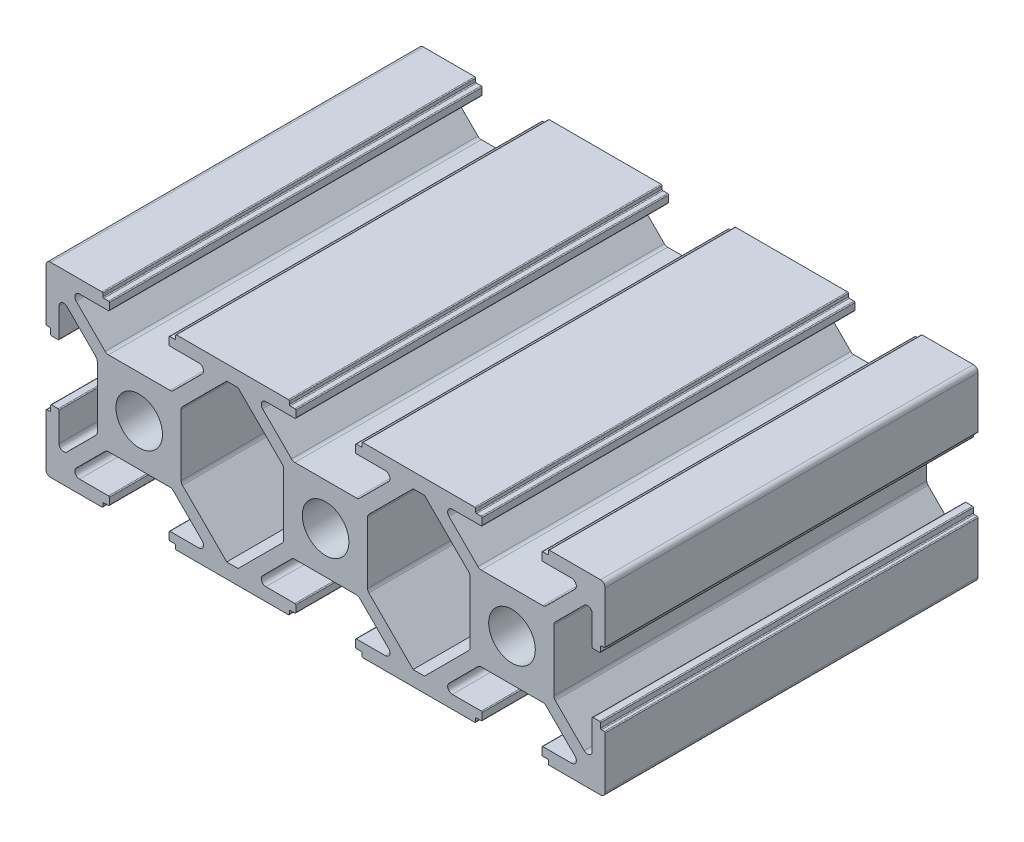
SolidWorks part; units mm, degrees
material "6061 Alaşım"
ref_plane "Ön Düzlem" through (0, 0, 0) normal (0, 0, 1) x (1, 0, 0)
ref_plane "Üst Düzlem" through (0, 0, 0) normal (0, 1, 0) x (1, 0, 0)
ref_plane "Sağ Düzlem" through (0, 0, 0) normal (1, 0, 0) x (0, 0, -1)
sketch "Çizim1" plane through (0, 0, 0) normal (0, 0, 1) x (1, 0, 0)
  line L0 (0, 0) -> (10, 10)
  line L1 (10, -10) -> (-10, -10)
  line L2 (10, -10) -> (10, 10)
  line L3 (10, 10) -> (-10, 10)
  line L4 (-10, -10) -> (-10, 10)
  line L5 (0, 10) -> (0, -10)
  line L6 (10, 0) -> (-10, 0)
  line L7 (4.5, 3.5101) -> (10, 9.0101)
  line L8 (3.5101, 4.5) -> (9.0101, 10)
  line L9 (10, 3.2) -> (8.6, 3.2)
  line L10 (8.6, 3.3) -> (8.6, 6.4029)
  line L11 (6.4029, 8.6) -> (3.3, 8.6)
  line L12 (3.2, 8.6) -> (3.2, 10)
  line L13 (3.6565, 4.6464) -> (6.7565, 7.7464)
  line L14 (7.7464, 6.7565) -> (4.6464, 3.6565)
  line L15 (3.2, 10) -> (9.5, 10)
  line L16 (10, 9.5) -> (10, 3.2)
  line L17 (4.5, 3.3029) -> (4.5, 0)
  line L18 (3.3029, 4.5) -> (0, 4.5)
  line L19 (3.3, 9.5) -> (3.8, 9.5)
  line L20 (3.9, 9.6) -> (3.9, 9.9)
  line L21 (3.2, 9.4) -> (3.2, 8.7)
  line L22 (4, 10) -> (9.5, 10)
  line L23 (9.5, 3.3) -> (9.5, 3.8)
  line L24 (9.6, 3.9) -> (9.9, 3.9)
  line L25 (8.7, 3.2) -> (9.4, 3.2)
  line L26 (10, 4) -> (10, 9.5)
  line L27 (0, 0) -> (10, -10)
  line L28 (3.3029, -4.5) -> (0, -4.5)
  line L29 (6.7565, -7.7464) -> (3.6565, -4.6464)
  line L30 (3.3, -8.6) -> (6.4029, -8.6)
  line L31 (3.2, -8.7) -> (3.2, -9.4)
  line L32 (3.3, -9.5) -> (3.8, -9.5)
  line L33 (3.9, -9.6) -> (3.9, -9.9)
  line L34 (4, -10) -> (9.5, -10)
  line L35 (10, -4) -> (10, -9.5)
  line L36 (9.6, -3.9) -> (9.9, -3.9)
  line L37 (9.5, -3.3) -> (9.5, -3.8)
  line L38 (9.4, -3.2) -> (8.7, -3.2)
  line L39 (8.6, -6.4029) -> (8.6, -3.3)
  line L40 (4.6464, -3.6565) -> (7.7464, -6.7565)
  line L41 (4.5, -3.3029) -> (4.5, 0)
  line L42 (0, 0) -> (-10, -10)
  line L43 (-4.5, -3.3029) -> (-4.5, 0)
  line L44 (-7.7464, -6.7565) -> (-4.6464, -3.6565) construction
  line L45 (-4.6464, 3.6565) -> (-9.3899, 8.4)
  line L46 (-9.3899, 8.4) -> (-10, 8.4)
  line L47 (-10, -8.4) -> (-9.3899, -8.4)
  line L48 (-9.3899, -8.4) -> (-4.6464, -3.6565)
  line L49 (-10, -4) -> (-10, -9.5)
  line L50 (-4, -10) -> (-9.5, -10)
  line L51 (-3.9, -9.6) -> (-3.9, -9.9)
  line L52 (-3.3, -9.5) -> (-3.8, -9.5)
  line L53 (-3.2, -9.4) -> (-3.2, -8.7)
  line L54 (-6.4029, -8.6) -> (-3.3, -8.6)
  line L55 (-3.6565, -4.6464) -> (-6.7565, -7.7464)
  line L56 (-3.3029, -4.5) -> (0, -4.5)
  line L57 (0, 0) -> (-10, 10)
  line L58 (-3.3029, 4.5) -> (0, 4.5)
  line L59 (-6.7565, 7.7464) -> (-3.6565, 4.6464)
  line L60 (-3.3, 8.6) -> (-6.4029, 8.6)
  line L61 (-3.2, 8.7) -> (-3.2, 9.4)
  line L62 (-3.3, 9.5) -> (-3.8, 9.5)
  line L63 (-3.9, 9.6) -> (-3.9, 9.9)
  line L64 (-4, 10) -> (-9.5, 10)
  line L65 (-10, 4) -> (-10, 9.5)
  line L70 (-4.6464, 3.6565) -> (-7.7464, 6.7565) construction
  line L71 (-4.5, 3.3029) -> (-4.5, 0)
  line L72 (-9.4, 3.2) -> (-8.7, 3.2) [skipped]
  line L73 (-8.6, 6.4029) -> (-8.6, 3.3) [skipped]
  line L74 (-9.5, 3.3) -> (-9.5, 3.8) [skipped]
  line L75 (-9.6, 3.9) -> (-9.9, 3.9) [skipped]
  line L76 (-8.6, -3.3) -> (-8.6, -6.4029) [skipped]
  line L77 (-9.6, -3.9) -> (-9.9, -3.9) [skipped]
  line L78 (-9.5, -3.3) -> (-9.5, -3.8) [skipped]
  line L79 (-8.7, -3.2) -> (-9.4, -3.2) [skipped]
  circle A0 centre (0, 0) radius 2.5
  arc A1 (10, 9.5) -> (9.5, 10) centre (9.5, 9.5) ccw
  arc A2 (4.5, 3.3029) -> (4.6464, 3.6565) centre (5, 3.3029) cw
  arc A3 (3.6565, 4.6464) -> (3.3029, 4.5) centre (3.3029, 5) cw
  arc A4 (8.6, 6.4029) -> (7.7464, 6.7565) centre (8.1, 6.4029) ccw
  arc A5 (6.4029, 8.6) -> (6.7565, 7.7464) centre (6.4029, 8.1) cw
  arc A6 (9.5, 3.8) -> (9.6, 3.9) centre (9.6, 3.8) cw
  arc A7 (9.9, 3.9) -> (10, 4) centre (9.9, 4) ccw
  arc A8 (8.7, 3.2) -> (8.6, 3.3) centre (8.7, 3.3) cw
  arc A9 (9.5, 3.3) -> (9.4, 3.2) centre (9.4, 3.3) cw
  arc A10 (3.3, 8.6) -> (3.2, 8.7) centre (3.3, 8.7) cw
  arc A11 (3.8, 9.5) -> (3.9, 9.6) centre (3.8, 9.6) ccw
  arc A12 (3.9, 9.9) -> (4, 10) centre (4, 9.9) cw
  arc A13 (3.3, 9.5) -> (3.2, 9.4) centre (3.3, 9.4) ccw
  arc A14 (3.3029, -4.5) -> (3.6565, -4.6464) centre (3.3029, -5) cw
  arc A15 (6.4029, -8.6) -> (6.7565, -7.7464) centre (6.4029, -8.1) ccw
  arc A16 (3.2, -8.7) -> (3.3, -8.6) centre (3.3, -8.7) cw
  arc A17 (3.3, -9.5) -> (3.2, -9.4) centre (3.3, -9.4) cw
  arc A18 (3.8, -9.5) -> (3.9, -9.6) centre (3.8, -9.6) cw
  arc A19 (3.9, -9.9) -> (4, -10) centre (4, -9.9) ccw
  arc A20 (9.5, -10) -> (10, -9.5) centre (9.5, -9.5) ccw
  arc A21 (9.9, -3.9) -> (10, -4) centre (9.9, -4) cw
  arc A22 (9.5, -3.8) -> (9.6, -3.9) centre (9.6, -3.8) ccw
  arc A23 (9.5, -3.3) -> (9.4, -3.2) centre (9.4, -3.3) ccw
  arc A24 (8.6, -3.3) -> (8.7, -3.2) centre (8.7, -3.3) cw
  arc A25 (8.6, -6.4029) -> (7.7464, -6.7565) centre (8.1, -6.4029) cw
  arc A26 (4.6464, -3.6565) -> (4.5, -3.3029) centre (5, -3.3029) cw
  arc A27 (-4.5, -3.3029) -> (-4.6464, -3.6565) centre (-5, -3.3029) cw
  arc A34 (-3.9, -9.9) -> (-4, -10) centre (-4, -9.9) cw
  arc A35 (-3.8, -9.5) -> (-3.9, -9.6) centre (-3.8, -9.6) ccw
  arc A36 (-3.3, -9.5) -> (-3.2, -9.4) centre (-3.3, -9.4) ccw
  arc A37 (-3.3, -8.6) -> (-3.2, -8.7) centre (-3.3, -8.7) cw
  arc A38 (-6.4029, -8.6) -> (-6.7565, -7.7464) centre (-6.4029, -8.1) cw
  arc A39 (-3.6565, -4.6464) -> (-3.3029, -4.5) centre (-3.3029, -5) cw
  arc A40 (-3.3029, 4.5) -> (-3.6565, 4.6464) centre (-3.3029, 5) cw
  arc A41 (-6.4029, 8.6) -> (-6.7565, 7.7464) centre (-6.4029, 8.1) ccw
  arc A42 (-3.2, 8.7) -> (-3.3, 8.6) centre (-3.3, 8.7) cw
  arc A43 (-3.3, 9.5) -> (-3.2, 9.4) centre (-3.3, 9.4) cw
  arc A44 (-3.8, 9.5) -> (-3.9, 9.6) centre (-3.8, 9.6) cw
  arc A45 (-3.9, 9.9) -> (-4, 10) centre (-4, 9.9) ccw
  arc A52 (-4.6464, 3.6565) -> (-4.5, 3.3029) centre (-5, 3.3029) cw
  arc A53 (-10, -9.5) -> (-9.5, -10) centre (-9.5, -9.5) ccw construction
  arc A54 (-9.5, 10) -> (-10, 9.5) centre (-9.5, 9.5) ccw construction
  arc A55 (-8.6, 3.3) -> (-8.7, 3.2) centre (-8.7, 3.3) cw [skipped]
  arc A56 (-9.5, 3.8) -> (-9.6, 3.9) centre (-9.6, 3.8) ccw [skipped]
  arc A57 (-9.9, 3.9) -> (-10, 4) centre (-9.9, 4) cw [skipped]
  arc A58 (-9.5, 3.3) -> (-9.4, 3.2) centre (-9.4, 3.3) ccw [skipped]
  arc A59 (-8.6, -6.4029) -> (-7.7464, -6.7565) centre (-8.1, -6.4029) ccw [skipped]
  arc A60 (-9.9, -3.9) -> (-10, -4) centre (-9.9, -4) ccw [skipped]
  arc A61 (-9.5, -3.8) -> (-9.6, -3.9) centre (-9.6, -3.8) cw [skipped]
  arc A62 (-9.5, -3.3) -> (-9.4, -3.2) centre (-9.4, -3.3) cw [skipped]
  arc A63 (-8.7, -3.2) -> (-8.6, -3.3) centre (-8.7, -3.3) cw [skipped]
  arc A64 (-8.6, 6.4029) -> (-7.7464, 6.7565) centre (-8.1, 6.4029) cw [skipped]
  point P0 (0, 0)
  point P32 (8.6, 7.6101)
  point P35 (7.6101, 8.6)
  point P41 (9.5, 3.9)
  point P44 (10, 3.9)
  point P50 (9.5, 3.2)
  point P62 (3.9, 9.5)
  point P65 (3.9, 10)
  point P68 (3.2, 9.5)
  point P198 (0, 0)
  dimension "D3" = 5
  dimension "D10" = 0.5
  dimension "D13" = 0.1
  dimension "D1" = 20
  dimension "D2" = 20
  dimension "D4" = 0.7
  dimension "D5" = 3.2
  dimension "D6" = 1.4
  dimension "D7" = 3.2
  dimension "D8" = 1.4
  dimension "D9" = 5.5
  dimension "D11" = 0.7
  dimension "D12" = 0.7
  dimension "D15" = 1.6
  dimension "D16" = 1.6
  dimension "D14" = 4
extrude "Yükseklik-Ekstrüzyon1" add sketch "Çizim1" against normal blind 40 contours L63 A45 L3 L57 A0 L5 L58 A40 L59 A41 L60 A42 L61 A43 L62 A44 | L45 A52 L71 L6 A0 L57 L4 L46 | L43 A27 L48 L47 L4 L42 A0 L6 | L55 A39 L56 L5 A0 L42 L1 A34 L51 A35 L52 A36 L53 A37 L54 A38 region at (-1.0063, 2.4294, 0) region at (-0.1295, -3.5, 0) region at (-2.4294, -1.0063, 0) region at (-3.5, 0.1295, 0)
mirror "Aynalama1" about plane through (-10, 0, -40) normal (1, 0, 0) of "Yükseklik-Ekstrüzyon1"
mirror "Aynalama2" about plane through (-20, 0, -40) normal (-1, 0, 0) of bodies 105
extrude "Yükseklik-Ekstrüzyon2" add sketch "Çizim1<7>" against normal blind 40 contours A3 L18 L5 A0 L0 A1 L3 L8 | L17 A2 L7 L2 A1 L0 A0 L6 | L19 A13 L12 A10 L11 A5 L8 L3 A12 L20 A11 | A9 L23 A6 L24 A7 L16 L7 A4 L10 A8 L9 | L40 A26 L41 L6 A0 L27 A20 L2 A21 L36 A22 L37 A23 L38 A24 L39 A25 | L1 A20 L27 A0 L5 L28 A14 L29 A15 L30 A16 L31 A17 L32 A18 L33 A19 region at (1.0058, 2.4283, 0) region at (5.9015, 5.7199, 0) region at (1.0058, -2.4283, 0) region at (3.5, -0.1284, 0) region at (9.2699, 5.9385, 0) region at (5.9385, 9.2699, 0)
sketch "Çizim1<7>" plane through (0, 0, 0) normal (0, 0, 1) x (1, 0, 0) same geometry as "Çizim1"
ref_plane "Düzlem1" through (-20, 0, 0) normal (1, 0, 0) x (0, 0, -1)
mirror "Aynalama3" about plane through (-20, 0, 0) normal (1, 0, 0) of "Yükseklik-Ekstrüzyon2"
